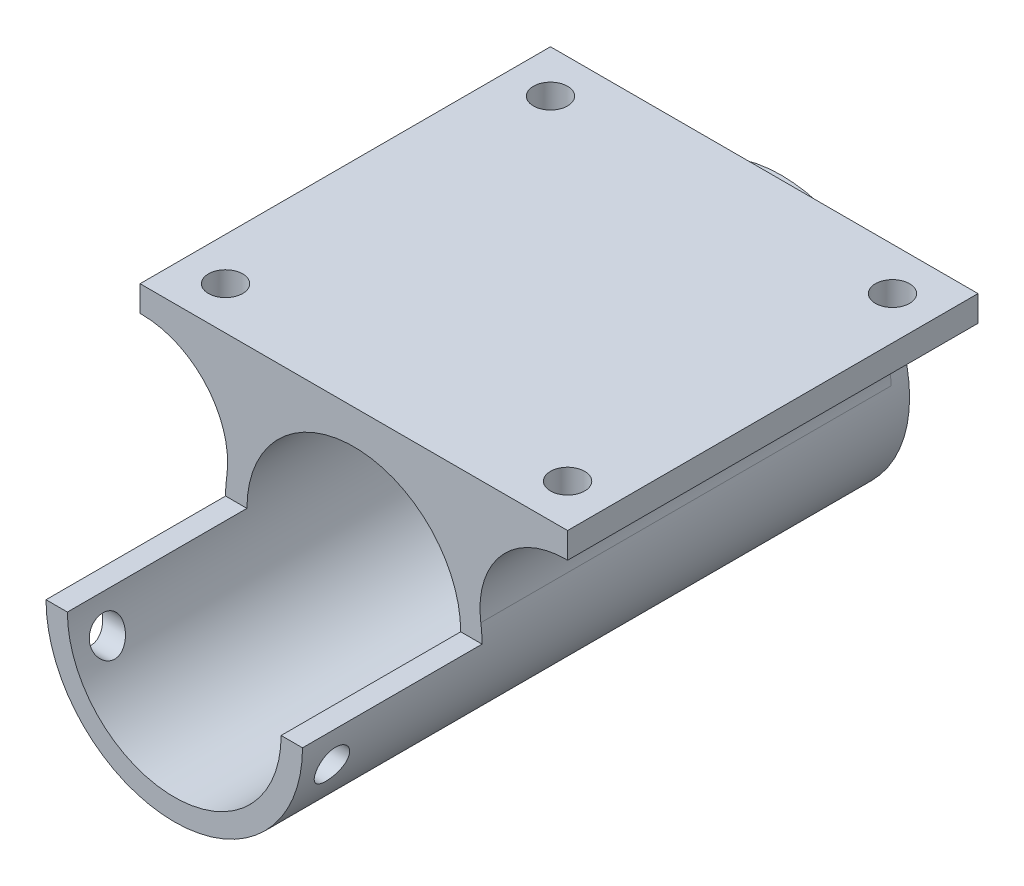
SolidWorks part; units mm, degrees
ref_plane "Front" through (0, 0, 0) normal (0, 0, 1) x (1, 0, 0)
ref_plane "Top" through (0, 0, 0) normal (0, 1, 0) x (1, 0, 0)
ref_plane "Right" through (0, 0, 0) normal (1, 0, 0) x (0, 0, -1)
sketch "Sketch1" plane through (0, 0, 0) normal (0, 0, 1) x (1, 0, 0)
  line L0 (24.7549, 13.4921) -> (25, 13.4921)
  line L1 (-25, 13.4921) -> (-24.7549, 13.4921)
  line L2 (-25, 13.4921) -> (-25, 16.5079)
  line L3 (-25, 16.5079) -> (25, 16.5079)
  line L4 (25, 13.4921) -> (25, 16.5079)
  circle A0 centre (0, 0) radius 12.5
  arc A1 (-14.8529, 2.0952) -> (14.8529, 2.0952) centre (0, 0) ccw
  arc A2 (24.7549, 13.4921) -> (14.8529, 2.0952) centre (24.7549, 3.4921) ccw
  arc A3 (-14.8529, 2.0952) -> (-24.7549, 13.4921) centre (-24.7549, 3.4921) ccw
  point P4 (0, 15)
  point P12 (6.5547, 13.4921)
  dimension "D1" = 25
  dimension "D2" = 30
  dimension "D4" = 10
  dimension "D3" = 50
extrude "Boss-Extrude1" add sketch "Sketch1" along normal blind 48
sketch "Sketch3" plane through (0, 0, 0) normal (0, 0, -1) x (-1, 0, 0)
  circle A0 centre (0, 0) radius 11
  circle A1 centre (0, 0) radius 15
  dimension "D1" = 22
  dimension "D2" = 30
extrude "Boss-Extrude3" add sketch "Sketch3" along normal blind 2
sketch "Sketch4" plane through (0, 16.5079, 0) normal (0, 1, 0) x (1, 0, 0)
  line L0 (25, -48) -> (25, 0) construction
  line L1 (25, 0) -> (-25, 0) construction
  line L2 (-25, -48) -> (-25, 0) construction
  line L3 (25, -48) -> (-25, -48) construction
  circle A0 centre (-20, -5) radius 2
  circle A1 centre (20, -5) radius 2
  circle A2 centre (20, -43) radius 2
  circle A3 centre (-20, -43) radius 2
  dimension "D1" = 4
  dimension "D2" = 4
  dimension "D3" = 4
  dimension "D4" = 4
  dimension "D5" = 5
  dimension "D6" = 5
  dimension "D7" = 5
  dimension "D8" = 5
  dimension "D9" = 5
  dimension "D10" = 5
  dimension "D11" = 5
  dimension "D12" = 5
extrude "Cut-Extrude1" cut sketch "Sketch4" against normal through all
sketch "Sketch5" plane through (0, 0, 48) normal (0, 0, 1) x (1, 0, 0)
  line L0 (-15, 0) -> (-12.5, 0)
  line L1 (12.5, 0) -> (15, 0)
  arc A0 (-12.5, 0) -> (12.5, 0) centre (0, 0) ccw
  arc A1 (-15, 0) -> (15, 0) centre (0, 0) ccw
  point P7 (0, 0)
  dimension "D1" = 25
  dimension "D2" = 30
extrude "Boss-Extrude4" add sketch "Sketch5" along normal blind 21
sketch "Sketch7" plane through (0, 0, 0) normal (1, 0, 0) x (0, 0, -1)
  line L0 (-69, 0) -> (-48, 0) construction
  line L1 (-69, 0) -> (-69, -15) construction
  circle A0 centre (-65, -4) radius 2
  dimension "D1" = 4
  dimension "D2" = 4
  dimension "D3" = 4
extrude "Cut-Extrude2" cut sketch "Sketch7" against normal through all both and the other way through all
